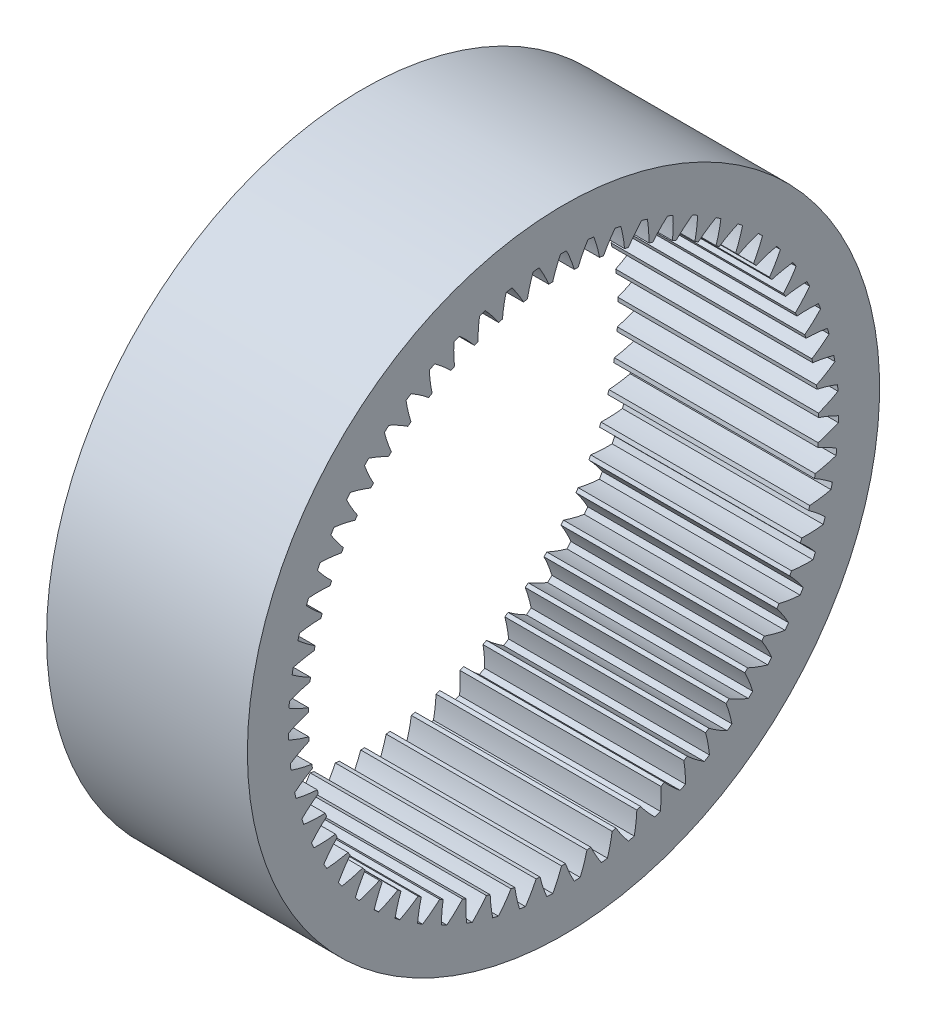
SolidWorks part; units mm, degrees
ref_plane "Plane1" through (0, 0, 0) normal (0, 0, 1) x (1, 0, 0)
ref_plane "Plane2" through (0, 0, 0) normal (0, 1, 0) x (1, 0, 0)
ref_plane "Plane3" through (0, 0, 0) normal (1, 0, 0) x (0, 0, -1)
sketch "HoldingSke" plane through (0, 0, 0) normal (0, 1, 0) x (1, 0, 0)
  line L0 (0, 0) -> (0.5, -0.866)
  line L1 (-15, 0) -> (100, 0) construction
  line L2 (0, 0) -> (-2.1039, 2.3779)
  line L3 (0, 0) -> (-11.863, 4.5341)
  line L4 (0, 0) -> (4.318, 7.479)
  line L5 (0, 0) -> (-23.7986, -8.8762)
  line L6 (0, 0) -> (-10.5278, -7.1032)
  line L7 (-2.1039, 2.3779) -> (3.3635, 27.1825)
  line L8 (-76.2, 3.3779) -> (-54.61, 3.3779)
  line L9 (-71.009, 38.7566) -> (-53.1078, 45.2721)
  line L10 (-76.2, 71.12) -> (104.1128, 71.12)
  line L11 (0, 0) -> (-12, 0)
  line L12 (-76.2, 101.6) -> (-76.162, 101.6)
  line L13 (24.9733, 27.94) -> (52.9518, 28.4284)
  line L14 (24.9733, 27.94) -> (24.9743, 27.94)
  line L15 (24.9733, 27.94) -> (100.4006, 29.5858)
  circle A0 centre (0, 0) radius 12.5
  circle A1 centre (0, 0) radius 12.7
  circle A2 centre (0, 0) radius 12.7
  dimension "MHD" = 25.4
  dimension "Hub_dia" = 25.4
  dimension "Diameter" = 25
  dimension "Num_teeth" = 60
  dimension "Pitch" = 1
  dimension "Overall_len" = 25.4
  dimension "Show_teeth" = 60
  dimension "Thickness" = 12.7
  dimension "OAL" = 25.4001
  dimension "T_dim" = 21.59
  dimension "Ap" = 20
  dimension "H" = 19.05
  dimension "Pitch_radius" = 180.3128
  dimension "Width" = 12
  dimension "Backlash" = 0.038
  dimension "Addendum_fac" = 1
  dimension "Dedendum_fac" = 1.25
  dimension "Clearance_fac" = 0.25
  dimension "Dedendum_add" = 0.001
  dimension "Module" = 1
sketch "BasProSke" plane through (0, 0, 0) normal (0, 1, 0) x (1, 0, 0)
  line L0 (-10, 0) -> (60, 0) construction
  line L1 (0, 29) -> (0, 31.2764)
  line L2 (0, 29) -> (22.815, 29)
  line L3 (22.815, 29) -> (22.815, 31.2764)
  line L4 (22.815, 31.2764) -> (0, 31.2764)
  dimension "Thickness" = 22.815
  dimension "Diameter" = 62.5528
  dimension "Inside_diameter" = 58
revolve "Base-Revolve" add sketch "BasProSke" angle 360 about L0
sketch "TooCutSke" plane through (0, 0, 0) normal (1, 0, 0) x (0, 0, -1)
  line L3 (0.8803, 29.9871) -> (0.8803, 53.6633) construction
  line L4 (0, 0) -> (0, 59.563) construction
  line L5 (0, 0) -> (-3.576, 68.2339) construction
  line L6 (-13.1633, 24.7167) -> (36.4631, 27.3175) construction
  circle A0 centre (0, 0) radius 30 construction
  circle A1 centre (0, 0) radius 31.251 construction
  circle A2 centre (0, 0) radius 25.3717 construction
  circle A3 centre (0, 0) radius 28.9746 construction
  arc A4 (1.2274, 28.9486) -> (0.3395, 31.2492) centre (-13.1633, 24.7167) ccw
  arc A5 (1.2274, 28.9486) -> (-1.2274, 28.9486) centre (0, 0) ccw
  arc A6 (0.3395, 31.2492) -> (-0.3395, 31.2492) centre (0, 0) ccw
  arc A7 (-0.3395, 31.2492) -> (-1.2274, 28.9486) centre (13.1633, 24.7167) ccw
  dimension "Pitch_dia" = 60
  dimension "Base_dia" = 50.7434
  dimension "Root_dia" = 62.502
  dimension "Overcut_dia" = 57.9492
  dimension "Flank_rad" = 15
  dimension "Half_ang" = 3
  dimension "Half_CT" = 0.8803
extrude "ToothCut" cut sketch "TooCutSke" along normal through all
fillet "Breaks" [suppressed] radius 0.1
fillet "RootFillets" [suppressed] radius 0.251
pattern_circular "TeethCuts" count 63 over 360 about axis through (-10, 0, 0) along (1, 0, 0) of "ToothCut"
scale "Scale1" scale about centroid uniform scaling yes scale factor 2
sketch "Sketch1" plane through (34.2225, 0, 0) normal (1, 0, 0) x (0, 0, -1)
  circle A0 centre (0, 0) radius 62.5528
sketch "Sketch2" plane through (34.2225, 0, 0) normal (1, 0, 0) x (0, 0, -1)
  circle A0 centre (0, 0) radius 72.5528
  circle A1 centre (0, 0) radius 62.5528
extrude "Boss-Extrude1" add sketch "Sketch2" against normal blind 45.63
scale "Scale2" scale about centroid uniform scaling yes scale factor 1.1
scale "Scale3" scale about centroid uniform scaling yes scale factor 1.01
scale "Scale4" scale about centroid uniform scaling yes scale factor 0.990099
scale "Scale5" scale about centroid uniform scaling yes scale factor 0.909091
scale "Scale6" scale about centroid uniform scaling yes scale factor 1.01
sketch "Sketch3" plane through (-11.6356, 0, 0) normal (-1, 0, 0) x (0, 0, 1)
  circle A0 centre (0, 0) radius 72.5528
  circle A1 centre (0, 0) radius 73.2783
extrude "Cut-Extrude1" cut sketch "Sketch3" against normal through all
equation "' \"Module@HoldingSke\" = 6.35"
equation "' \"Num_teeth@HoldingSke\" = 24"
equation "' \"Ap@HoldingSke\" =  14.5"
equation "' \"Ap@HoldingSke\" = 14.5"
equation "' \"Width@HoldingSke\" = 12"
equation "' \"Diameter@HoldingSke\" = 8 * 25.4"
equation "' \"Show_teeth@HoldingSke\" = 100"
equation "' \"Backlash@HoldingSke\" = 0.009 * 25.4"
equation "' \"Addendum_fac@HoldingSke\" = 1.0"
equation "' \"Dedendum_fac@HoldingSke\" = 1.25"
equation "' \"Dedendum_add@HoldingSke\" = 0.00005 * 25.4"
equation "' \"Clearance_fac@HoldingSke\" = 0.25"
equation "\"Pitch@HoldingSke\" = 1 / \"Module@HoldingSke\" "
equation "\"Overcut_dia@TooCutSke\" = (\"Num_teeth@HoldingSke\" - 2 * \"Addendum_fac@HoldingSke\") / \"Pitch@HoldingSke\" - 0.002 * 25.4"
equation "\"Pitch_dia@TooCutSke\" = \"Num_teeth@HoldingSke\" / \"Pitch@HoldingSke\""
equation "\"Base_dia@TooCutSke\" = \"Num_teeth@HoldingSke\" / \"Pitch@HoldingSke\" * cos((\"Ap@HoldingSke\"  * 3.14159265 / 180)) * 0.90"
equation "\"Root_dia@TooCutSke\" = \"Num_teeth@HoldingSke\"  / \"Pitch@HoldingSke\" + 2 *  \"Dedendum_fac@HoldingSke\"/ \"Pitch@HoldingSke\" + \"Dedendum_add@HoldingSke\" * 2"
equation "\"Half_ang@TooCutSke\" = 180 / \"Num_teeth@HoldingSke\""
equation "\"Half_CT@TooCutSke\" = \"Num_teeth@HoldingSke\" / \"Pitch@HoldingSke\" * sin((3.14159265 / 2 / \"Num_teeth@HoldingSke\")) / 2 + 10 * \"Backlash@HoldingSke\" / 4"
equation "\"Flank_rad@TooCutSke\" = \"Num_teeth@HoldingSke\" / \"Pitch@HoldingSke\" / 4"
equation "\"Radius@RootFillets\"= \"Clearance_fac@HoldingSke\" / \"Pitch@HoldingSke\" + \"Dedendum_add@HoldingSke\""
equation "\"Break_rad@Breaks\" = 0.02 / \"Pitch@HoldingSke\" * 5"
equation "\"Diameter@BasProSke\" = \"Num_teeth@HoldingSke\"  / \"Pitch@HoldingSke\" + 2 *  \"Dedendum_fac@HoldingSke\"/ \"Pitch@HoldingSke\" + \"Dedendum_add@HoldingSke\" * 2 + 0.002 * 25.4"
equation "\"Diameter@BasProSke\" = ((sgn( \"Diameter@BasProSke\"  - \"Diameter@HoldingSke\" )+1)*( \"Diameter@BasProSke\"  - \"Diameter@HoldingSke\" ))/2 + \"Diameter@HoldingSke\""
equation "\"Inside_diameter@BasProSke\" =  (\"Num_teeth@HoldingSke\" - 2 * \"Addendum_fac@HoldingSke\") / \"Pitch@HoldingSke\" "
